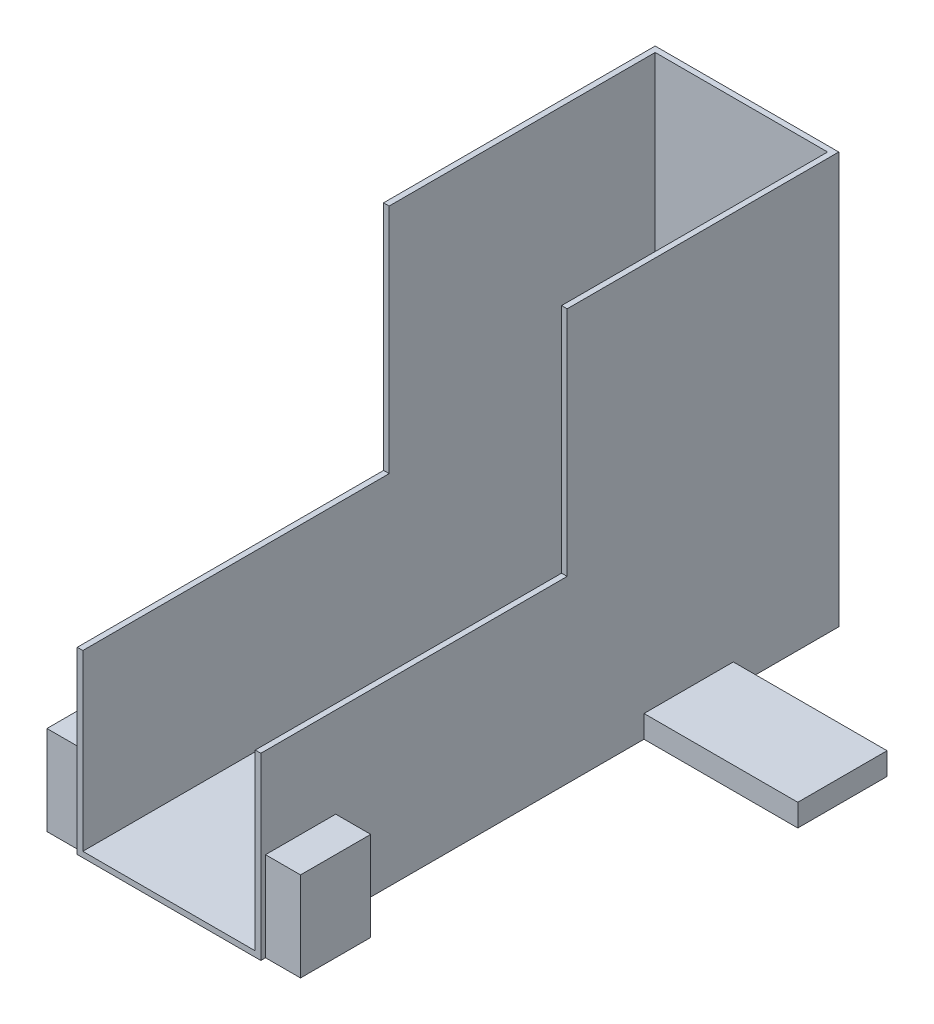
SolidWorks part; units mm, degrees
ref_plane "Front Plane" through (0, 0, 0) normal (0, 0, 1) x (1, 0, 0)
ref_plane "Top Plane" through (0, 0, 0) normal (0, 1, 0) x (1, 0, 0)
ref_plane "Right Plane" through (0, 0, 0) normal (1, 0, 0) x (0, 0, -1)
sketch "Sketch15" plane through (0, 0, 0) normal (1, 0, 0) x (0, 0, -1)
  line B0 (0, 0) -> (-657.6158, 0)
  line B1 (0, 0) -> (0, 467.9127)
  line B2 (-657.6158, 0) -> (-657.6158, 204.2049)
  line B3 (0, 467.9127) -> (-309.0338, 467.9127)
  line B4 (-309.0338, 204.2049) -> (-657.6158, 204.2049)
  line B5 (-309.0338, 204.2049) -> (-309.0338, 467.9127)
sketch_block_instance "frameSideview-1"
sketch_block "Block1"
extrude "Boss-Extrude1" add sketch "Sketch15" against normal blind 6.35
sketch "Sketch16" plane through (0, 0, 0) normal (0, 1, 0) x (1, 0, 0)
  line B0 (0, -685.8) -> (196.1896, -685.8)
  line B1 (0, -685.8) -> (0, 0)
  line B2 (196.1896, -685.8) -> (196.1896, 0)
  line B3 (0, -685.8) -> (196.1896, 0) construction
  line B4 (0, 0) -> (196.1896, -685.8) construction
sketch_block_instance "Drivebase_gearbox_Gap-1"
sketch_block "Drivebase_gearbox_Gap"
sketch "Sketch17" plane through (0, 0, 0) normal (0, 1, 0) x (1, 0, 0)
  line L0 (196.1896, -685.8) -> (196.1896, 0) construction
  line L1 (0, 0) -> (196.1896, 0)
  line L2 (0, 0) -> (0, -657.6158)
  line L3 (0, -657.6158) -> (196.1896, -657.6158)
  line L4 (196.1896, 0) -> (196.1896, -657.6158)
  line L5 (-6.35, -657.6158) -> (0, -657.6158) construction
extrude "Boss-Extrude2" add sketch "Sketch17" along normal blind 6.35
ref_plane "Plane1" through (98.0948, 0, 0) normal (1, 0, 0) x (0, 0, -1)
mirror "Mirror1" about plane through (98.0948, 0, 0) normal (1, 0, 0) of "Boss-Extrude1"
sketch "Sketch18" plane through (0, 0, 0) normal (0, 0, -1) x (-1, 0, 0)
  line L1 (-202.5396, 467.9127) -> (6.35, 467.9127)
  line L2 (-202.5396, 467.9127) -> (-202.5396, 0)
  line L3 (-202.5396, 0) -> (6.35, 0)
  line L4 (6.35, 467.9127) -> (6.35, 0)
extrude "Boss-Extrude3" add sketch "Sketch18" against normal blind 6.35
sketch "Sketch19" plane through (0, 0, 0) normal (0, 1, 0) x (1, 0, 0)
  line L1 (98.0948, -253.8595) -> (98.0948, 253.8595) construction
  line B0 (98.0948, -323.1859) -> (98.0948, 49676.8141) construction
  line B1 (-181.3052, -119.9859) -> (377.4948, -119.9859)
  line B2 (-181.3052, -119.9859) -> (-181.3052, -221.5859)
  line B3 (-181.3052, -221.5859) -> (377.4948, -221.5859)
  line B4 (377.4948, -119.9859) -> (377.4948, -221.5859)
  line B5 (-46.1772, -572.3724) -> (242.3668, -572.3724)
  line B6 (-46.1772, -572.3724) -> (-46.1772, -652.2613)
  line B7 (-46.1772, -652.2613) -> (242.3668, -652.2613)
  line B8 (242.3668, -572.3724) -> (242.3668, -652.2613)
sketch_block_instance "frameTopView-1"
sketch_block "frameTopView"
sketch "Sketch20" plane through (0, 0, 0) normal (0, 1, 0) x (1, 0, 0)
  line L0 (-181.3052, -119.9859) -> (377.4948, -119.9859) construction
  line L1 (-181.3052, -221.5859) -> (-6.35, -221.5859)
  line L2 (-181.3052, -221.5859) -> (-181.3052, -119.9859)
  line L3 (-181.3052, -119.9859) -> (-6.35, -119.9859)
  line L4 (-6.35, -221.5859) -> (-6.35, -119.9859)
  line L5 (-6.35, 0) -> (-6.35, -309.0338) construction
  line L6 (-181.3052, -221.5859) -> (377.4948, -221.5859) construction
  line L7 (377.4948, -119.9859) -> (202.5396, -119.9859)
  line L8 (377.4948, -119.9859) -> (377.4948, -221.5859)
  line L9 (377.4948, -221.5859) -> (202.5396, -221.5859)
  line L10 (202.5396, -119.9859) -> (202.5396, -221.5859)
  line L11 (202.5396, 0) -> (202.5396, -309.0338) construction
extrude "Boss-Extrude4" add sketch "Sketch20" along normal blind 25.4
sketch "Sketch22" plane through (0, 0, 0) normal (0, 1, 0) x (1, 0, 0)
  line L0 (-46.1772, -652.2613) -> (242.3668, -652.2613) construction
  line L1 (-46.1772, -572.3724) -> (-6.35, -572.3724)
  line L2 (-46.1772, -572.3724) -> (-46.1772, -652.2613)
  line L3 (-46.1772, -652.2613) -> (-6.35, -652.2613)
  line L4 (-6.35, -572.3724) -> (-6.35, -652.2613)
  line L5 (-6.35, -309.0338) -> (-6.35, -657.6158) construction
  line L6 (202.5396, -309.0338) -> (202.5396, -657.6158) construction
  line L7 (242.3668, -572.3724) -> (202.5396, -572.3724)
  line L8 (242.3668, -572.3724) -> (242.3668, -652.2613)
  line L9 (242.3668, -652.2613) -> (202.5396, -652.2613)
  line L10 (202.5396, -572.3724) -> (202.5396, -652.2613)
extrude "Boss-Extrude5" add sketch "Sketch22" along normal blind 101.6
